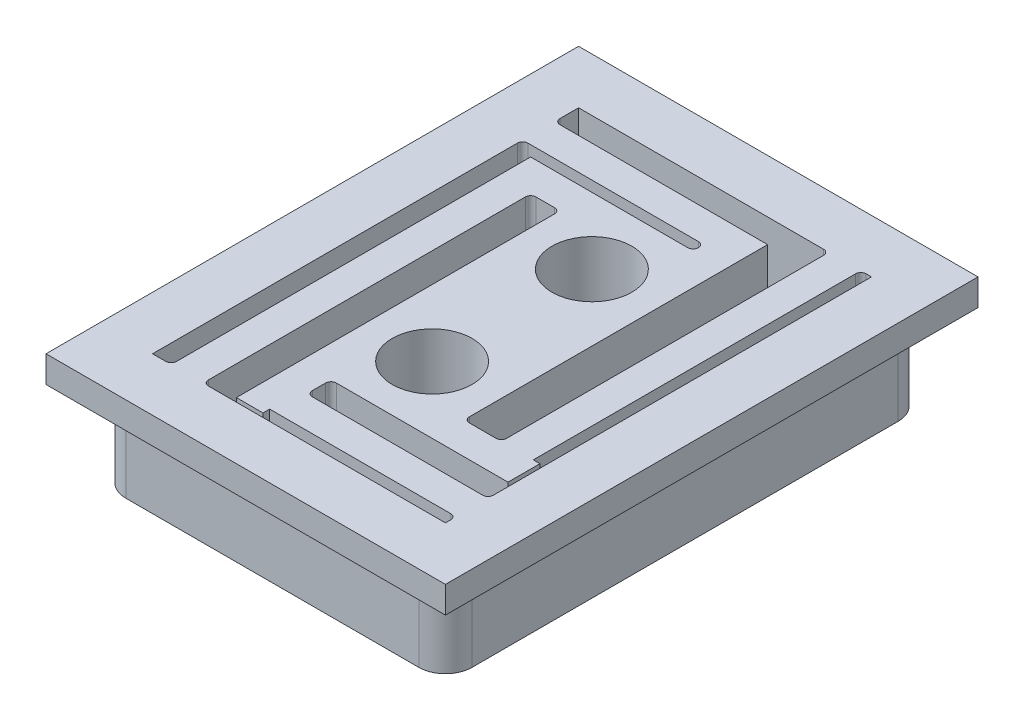
SolidWorks part; units mm, degrees
ref_plane "Front Plane" through (0, 0, 0) normal (0, 0, 1) x (1, 0, 0)
ref_plane "Top Plane" through (0, 0, 0) normal (0, 1, 0) x (1, 0, 0)
ref_plane "Right Plane" through (0, 0, 0) normal (1, 0, 0) x (0, 0, -1)
sketch "Sketch1" plane through (0, 0, 0) normal (0, 1, 0) x (1, 0, 0)
  line L1 (-6.5, -9) -> (6.5, -9)
  line L2 (-6.5, -9) -> (-6.5, 9)
  line L3 (-6.5, 9) -> (6.5, 9)
  line L4 (6.5, -9) -> (6.5, 9)
  line L5 (-6.5, -9) -> (6.5, 9) construction
  line L6 (-6.5, 9) -> (6.5, -9) construction
  point P0 (0, 0)
  dimension "D1" = 18
  dimension "D2" = 13
extrude "Boss-Extrude1" add sketch "Sketch1" along normal blind 3.2
sketch "Sketch2" plane through (0, 3.2, 0) normal (0, 1, 0) x (1, 0, 0)
  line L8 (7.5, -10) -> (7.5, 10)
  line L9 (7.5, 10) -> (-7.5, 10)
  line L10 (-7.5, 10) -> (-7.5, -10)
  line L11 (-7.5, -10) -> (7.5, -10)
  line L12 (7.5, -10) -> (7.5, 10)
  line L13 (7.5, 10) -> (-7.5, 10)
  line L14 (-7.5, 10) -> (-7.5, -10)
  line L15 (-7.5, -10) -> (7.5, -10)
  dimension "D1" = 1
extrude "Boss-Extrude2" add sketch "Sketch2" along normal blind 1
sketch "Sketch3" plane through (0, 0, 0) normal (0, -1, 0) x (1, 0, 0)
  line L0 (0, -3) -> (0, 3)
  line L1 (1.9, 5.5) -> (1.9, 7) construction
  line L2 (1.3, 5.5) -> (1.3, 6.4) construction
  line L3 (-1.9, -5.5) -> (-1.9, -6.5) construction
  line L4 (-1.3, -5.5) -> (-1.3, -5.9) construction
  line L5 (-4.5, -8) -> (-4.5, 4.9) construction
  line L6 (2.5, -5.5) -> (-2.5, -5.5)
  line L7 (2.5, -5.5) -> (2.5, 5.5)
  line L8 (2.5, 5.5) -> (-2.5, 5.5)
  line L9 (5.5, -8) -> (5.5, 8)
  line L10 (5.5, 8) -> (-5.5, 8)
  line L11 (-5.5, 8) -> (-5.5, -8)
  line L12 (-5.5, -8) -> (5.5, -8)
  line L13 (5.5, -8) -> (5.5, 8)
  line L14 (5.5, 8) -> (-5.5, 8)
  line L15 (-5.5, 8) -> (-5.5, -8)
  line L16 (-5.5, -8) -> (5.5, -8)
  line L17 (-2.5, -5.5) -> (-2.5, 5.5)
  line L18 (2.5, -5.5) -> (-2.5, 5.5) construction
  line L19 (2.5, 5.5) -> (-2.5, -5.5) construction
  line L20 (-4.5, 4.9) -> (-2.5, 4.9) construction
  line L21 (4.2, 8) -> (4.2, -4.9) construction
  line L22 (4.2, -4.9) -> (2.5, -4.9) construction
  line L23 (1.9, 5.5) -> (1.9, 7) construction
  line L24 (1.9, 7) -> (-5.5, 7) construction
  line L25 (-1.9, -5.5) -> (-1.9, -6.5) construction
  line L26 (-1.9, -6.5) -> (5.5, -6.5) construction
  line L27 (-3.9, -8) -> (-3.9, 4.3)
  line L28 (-3.9, 4.3) -> (-2.5, 4.3)
  line L29 (-2.5, -5.5) -> (-2.5, -7.1)
  line L30 (-2.5, -7.1) -> (5.5, -7.1)
  line L31 (3.6, 8) -> (3.6, -4.3)
  line L32 (3.6, -4.3) -> (2.5, -4.3)
  line L33 (2.5, 5.5) -> (2.5, 7.6)
  line L34 (2.5, 7.6) -> (-5.5, 7.6)
  line L35 (-5.1, -8) -> (-5.1, 5.5)
  line L36 (-5.1, 5.5) -> (-2.5, 5.5)
  line L37 (-1.3, -5.5) -> (-1.3, -5.9)
  line L38 (-1.3, -5.9) -> (5.5, -5.9)
  line L39 (4.8, 8) -> (4.8, -5.5)
  line L40 (4.8, -5.5) -> (2.5, -5.5)
  line L41 (1.3, 5.5) -> (1.3, 6.4)
  line L42 (1.3, 6.4) -> (-5.5, 6.4)
  line L43 (-5.1, 5.5) -> (-5.35, 5.5)
  line L44 (-5.35, 5.5) -> (-5.35, 4.3)
  line L45 (-5.35, 4.3) -> (-5.1, 4.3)
  line L46 (2.5, 7.6) -> (2.5, 7.85)
  line L47 (2.5, 7.85) -> (1.5, 7.85)
  line L48 (1.5, 7.85) -> (1.5, 7.6)
  line L49 (-4.5, 4.9) -> (-2.5, 4.9) construction
  line L50 (-3.9, 4.3) -> (-2.5, 4.3) construction
  line L51 (4.2, -4.9) -> (2.5, -4.9) construction
  line L52 (3.6, -4.3) -> (2.5, -4.3) construction
  circle A0 centre (0, 3) radius 1.5
  circle A1 centre (0, -3) radius 1.5
  point P4 (0, 0)
  point P7 (0, 0)
  dimension "D2" = 3
  dimension "D1" = 6
  dimension "D4" = 11
  dimension "D5" = 5
  dimension "D6" = 1
  dimension "D7" = 1.3
  dimension "D8" = 1
  dimension "D9" = 1.5
  dimension "D12" = 0.25
  dimension "D13" = 1
  dimension "D14" = 0.25
  dimension "D15" = 0.6
  dimension "D16" = 0.6
  dimension "D17" = 0.6
  dimension "D18" = 0.6
  dimension "D3" = 1
  dimension "D10" = 0.6
  dimension "D11" = 0.6
extrude "Cut-Extrude1" cut sketch "Sketch3" against normal through all contours L30 L29 L17 L28 L27 L16 L13 | L39 L40 L7 L6 L37 L38 L13 L14 | L48 L47 L46 L33 L7 L32 L31 L14 L15 L34 | L45 L44 L43 L36 L8 L41 L42 L15 L16 L35 | A0 | A1 region at (3.65, 0, -5.6547) region at (2.653, 0, 0.6) region at (-2.6548, 0, -6.3) region at (-0.6, 0, 5.6592)
fillet "Fillet1" radius 0.2 16 edges at (-5.1, 2.1, -8) (-3.9, 2.1, -8) (-5.5, 2.1, 6.4) (-5.5, 2.1, 7.6) (4.8, 2.1, 8) (3.6, 2.1, 8) (-3.9, 2.1, 4.3) (-2.5, 2.1, 4.3) (1.3, 2.1, 5.5) (1.3, 2.1, 6.4) (5.5, 2.1, -7.1) (5.5, 2.1, -5.9) (-1.3, 2.1, -5.9) (-1.3, 2.1, -5.5) (3.6, 2.1, -4.3) (2.5, 2.1, -4.3)
fillet "Fillet2" radius 1 4 edges at (-6.5, 1.6, 9) (-6.5, 1.6, -9) (6.5, 1.6, -9) (6.5, 1.6, 9)
mirror "Mirror1" about plane through (-7.5, 4.2, -10) normal (1, 0, 0) of bodies 103
delete or keep bodies "Body-Delete/Keep 1" type keep bodies bodies 104
